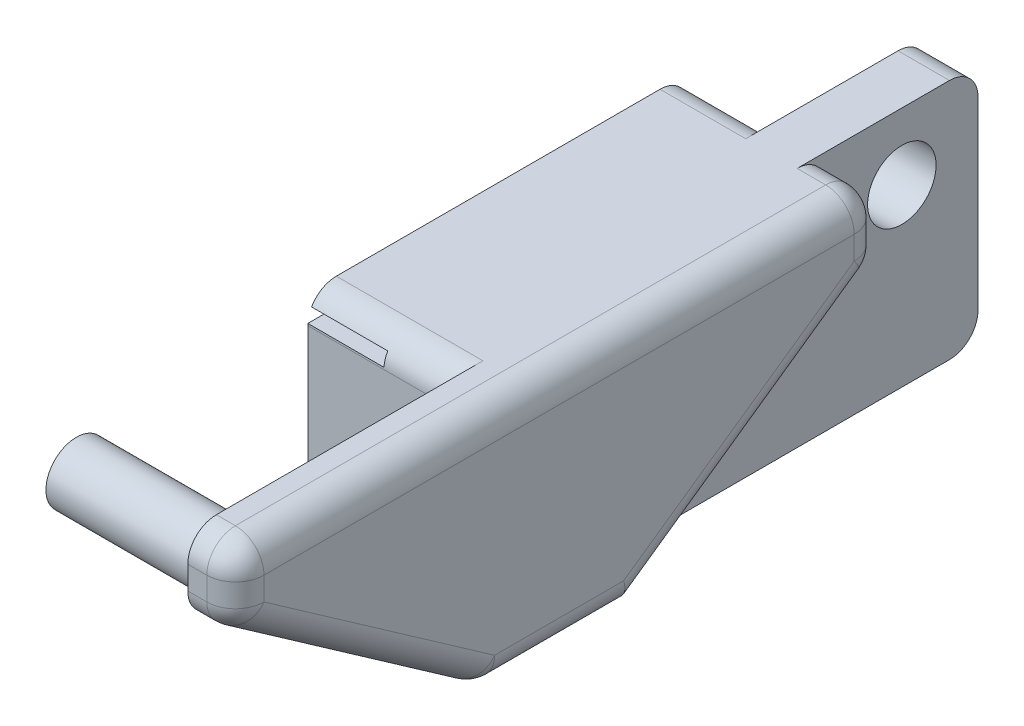
SolidWorks part; units mm, degrees
ref_plane "Front Plane" through (0, 0, 0) normal (0, 0, 1) x (1, 0, 0)
ref_plane "Top Plane" through (0, 0, 0) normal (0, 1, 0) x (1, 0, 0)
ref_plane "Right Plane" through (0, 0, 0) normal (1, 0, 0) x (0, 0, -1)
sketch "Sketch1" plane through (0, 0, 0) normal (0, 1, 0) x (1, 0, 0)
  line L0 (-28.7782, 15.5442) -> (-24.2782, 15.5442)
  line L1 (-24.2782, 15.5442) -> (-24.2782, 23.5442)
  line L2 (-24.2782, 23.5442) -> (-21.5782, 23.5442)
  line L3 (-21.5782, 23.5442) -> (-21.5782, 15.5442)
  line L4 (-21.5782, 15.5442) -> (-18.5782, 15.5442)
  line L5 (-18.5782, 15.5442) -> (-18.5782, -18.4558)
  line L6 (-18.5782, -18.4558) -> (-21.0782, -18.4558)
  line L7 (-21.0782, -18.4558) -> (-21.0782, -4.4558)
  line L10 (-21.0782, -4.4558) -> (-28.7782, -4.4558)
  line L11 (-28.7782, -4.4558) -> (-28.7782, 15.5442)
  dimension "D1" = 10.2
  dimension "D2" = 3
  dimension "D3" = 4.5
  dimension "D4" = 8
  dimension "D5" = 14
  dimension "D6" = 7.7
  dimension "D7" = 42
extrude "Boss-Extrude1" add sketch "Sketch1" along normal blind 12.7
sketch "Sketch2" plane through (-28.7782, 0, 0) normal (-1, 0, 0) x (0, 0, 1)
  line L0 (-23.5442, 12.7) -> (-23.5442, 0)
  line L1 (-23.5442, 0) -> (12.1247, 0)
  line L2 (12.1247, 0) -> (18.4558, 9.2)
  line L3 (18.4558, 9.2) -> (18.4558, 12.7)
  line L4 (18.4558, 12.7) -> (-23.5442, 12.7)
  line L5 (-23.5442, 9.2) -> (18.4558, 9.2) construction
  line L6 (-19.5442, 12.7) -> (-19.5442, 0) construction
  line L7 (-12.2942, 12.7) -> (-12.2942, 0) construction
  line L8 (15.2058, 12.7) -> (15.2058, 4.4773) construction
  line L9 (-15.5442, 5.7649) -> (-7.0404, 0)
  line L11 (4.4558, 0) -> (4.4558, 12.7)
  line L13 (-15.5442, 12.7) -> (-15.5442, 5.7649)
  line L14 (-15.5442, 12.7) -> (4.4558, 12.7)
  line L15 (12.1247, 0) -> (18.4558, 0)
  line L16 (-15.5442, 0) -> (4.4558, 0) construction
  line L17 (-15.5442, 12.7) -> (4.4558, 12.7) construction
  line L18 (-7.0404, 0) -> (4.4558, 0)
  line L19 (-15.5442, 5.7649) -> (-15.5442, 0)
  line L20 (-15.5442, 0) -> (-7.0404, 0)
  line L21 (18.4558, 0) -> (18.4558, 9.2)
  line L22 (15.2058, 10.8) -> (-23.5442, 10.8) construction
  line L23 (-23.5442, 11.3) -> (18.4558, 11.3) construction
  line L25 (18.4558, 11.95) -> (-23.5442, 11.95)
  line L26 (18.4558, 11.95) -> (18.4558, 11.3)
  line L27 (18.4558, 11.3) -> (-23.5442, 11.3)
  line L28 (-23.5442, 11.95) -> (-23.5442, 11.3)
  circle A3 centre (15.2058, 9.2) radius 1.6
  circle A4 centre (-12.2942, 9.2) radius 1.6
  circle A5 centre (-19.5442, 9.2) radius 1.8
  line M18 (-15.5442, 0) -> (4.4558, 0)
  line M21 (-15.5442, 12.7) -> (-15.5442, 0)
  dimension "D9" = 0.5
  dimension "D1" = 12.7
  dimension "D2" = 3.5
  dimension "D3" = 4
  dimension "D4" = 11.25
  dimension "D5" = 8
  dimension "D6" = 6.5
  dimension "D7" = 14
  dimension "D8" = 42
  dimension "D10" = 0.65
  dimension "D11" = 8.5038
extrude "Cut-Extrude2" cut sketch "Sketch2" along direction (1, 0, 0) on the side against the normal up to surface (4.5 mm away) contours L9 M21 M18 region at (-28.7782, 1.9216, -12.7096) up to face at (-24.2782, 6.35, -19.5442)
extrude "Cut-Extrude3" cut sketch "Sketch2<4>" against normal through all contours L15 L21 L2 region at (-28.7782, 3.0667, 16.3454)
sketch "Sketch2<4>" plane through (-28.7782, 0, 0) normal (-1, 0, 0) x (0, 0, 1) same geometry as "Sketch2"
extrude "Boss-Extrude2" add sketch "Sketch2<5>" along normal blind 9.1 from surface contours A3 region at (-28.7782, 9.2, 15.2058) starting at face at (-21.0782, 6.92, 11.5896)
sketch "Sketch2<5>" plane through (-28.7782, 0, 0) normal (-1, 0, 0) x (0, 0, 1) same geometry as "Sketch2"
extrude "Cut-Extrude4" cut sketch "Sketch2<6>" against normal through all contours A5 region at (-28.7782, 9.2, -19.5442)
sketch "Sketch2<6>" plane through (-28.7782, 0, 0) normal (-1, 0, 0) x (0, 0, 1) same geometry as "Sketch2"
extrude "Boss-Extrude3" add sketch "Sketch2<7>" along normal blind 1.4 contours A4 region at (-28.7782, 9.2, -12.2942)
sketch "Sketch2<7>" plane through (-28.7782, 0, 0) normal (-1, 0, 0) x (0, 0, 1) same geometry as "Sketch2"
extrude "Cut-Extrude5" cut sketch "Sketch2<8>" against normal blind 4 from surface contours L25 L28 L27 L26 starting at face at (-28.7782, 9.2, -13.8942)
sketch "Sketch2<8>" plane through (-28.7782, 0, 0) normal (-1, 0, 0) x (0, 0, 1) same geometry as "Sketch2"
sketch "Sketch3" plane through (-18.5782, 0, 0) normal (1, 0, 0) x (0, 0, -1)
  line L0 (15.5442, 12.7) -> (-18.4558, 12.7)
  line L3 (-18.4558, 0) -> (15.5442, 0)
  line L5 (15.5442, 12.7) -> (15.5442, 9.2)
  line L6 (15.5442, 9.2) -> (2.4052, 0)
  line L7 (2.4052, 0) -> (-1.4558, 0)
  line L8 (15.5442, 9.2) -> (15.5442, 0)
  line L9 (15.5442, 0) -> (2.4052, 0)
  line L10 (-1.4558, 12.7) -> (-1.4558, 0)
  line L11 (-18.4558, 0) -> (-5.3168, 0)
  line L12 (-18.4558, 9.2) -> (-18.4558, 0)
  line L13 (-18.4558, 9.2) -> (-5.3168, 0)
  line L14 (-18.4558, 12.7) -> (-18.4558, 9.2)
  line M7 (-18.4558, 9.2) -> (-12.1247, 0)
  line M8 (-12.1247, 0) -> (15.5442, 0)
  line M9 (15.5442, 0) -> (15.5442, 12.7)
  dimension "D1" = 13.139
  dimension "D3" = 9.2
  dimension "D4" = 12.7
extrude "Cut-Extrude6" cut sketch "Sketch3" against normal up to surface (3 mm away) contours L6 L3 M9 | L12 L3 M7 | L13 M7 M8 region at (-18.5782, 3.0667, -11.1645) region at (-18.5782, 3.0667, 16.3454) region at (-18.5782, 3.0667, 11.9658) up to face at (-21.5782, 9.2, -17.7442)
sketch "Sketch4" plane through (0, 0, 0) normal (0, -1, 0) x (1, 0, 0)
  line L0 (-22.9282, -23.5442) -> (-22.9282, 4.4558) construction
  line L1 (-21.5782, -23.5442) -> (-24.2782, -23.5442) construction
  line L2 (-28.7782, 4.4558) -> (-21.0782, 4.4558) construction
  line L4 (-22.1782, -23.5442) -> (-23.6782, -23.5442)
  line L5 (-22.1782, -23.5442) -> (-22.1782, 4.4558)
  line L6 (-22.1782, 4.4558) -> (-23.6782, 4.4558)
  line L7 (-23.6782, -23.5442) -> (-23.6782, 4.4558)
  dimension "D1" = 0.75
  dimension "D2" = 0.75
extrude "Cut-Extrude7" cut sketch "Sketch4" against normal blind 3
sketch "Sketch6" plane through (0, 0, 0) normal (0, -1, 0) x (-1, 0, 0)
  line L1 (23.6782, -4.4558) -> (21.5782, -4.4558)
  line L2 (23.6782, -4.4558) -> (23.6782, 2.4052)
  line L3 (23.6782, 2.4052) -> (21.5782, 2.4052)
  line L4 (21.5782, -4.4558) -> (21.5782, 2.4052)
extrude "Boss-Extrude4" add sketch "Sketch6" against normal blind 1
sketch "Sketch8" plane through (-28.7782, 0, 0) normal (-1, 0, 0) x (0, 0, 1)
  line L0 (1.4558, 12.7) -> (-15.5442, 12.7)
  line L1 (-15.5442, 0) -> (1.4558, 0)
  line L7 (1.4558, 12.7) -> (1.4558, 0)
  line L8 (-15.5442, 0) -> (-2.4052, 0)
  line L9 (-15.5442, 9.2) -> (-15.5442, 0)
  line L10 (-15.5442, 9.2) -> (-2.4052, 0)
  line L11 (-15.5442, 12.7) -> (-15.5442, 9.2)
  line M7 (-15.5442, 5.7649) -> (-7.0404, 0)
  line M9 (-7.0404, 0) -> (4.4558, 0)
  line M19 (-15.5442, 11.3) -> (-15.5442, 5.7649)
  dimension "D1" = 13.139
  dimension "D2" = 12.7
  dimension "D3" = 9.2
  dimension "D4" = 17
extrude "Cut-Extrude8" cut sketch "Sketch8" against normal up to surface (4.5 mm away) contours L9 L1 M7 | L10 M19 M7 M9 region at (-28.7782, 3.8479, -10.1104) region at (-28.7782, 1.9216, -12.7096) up to face at (-24.2782, 9.2, -21.3442)
fillet "Fillet1" radius 1.5 19 edges at (-24.9282, 0, 4.4558) (-24.9282, 12.7, 4.4558) (-21.8782, 0, -23.5442) (-23.9782, 0, -23.5442) (-22.9282, 12.7, -23.5442) (-18.5782, 10.95, 18.4558) (-19.8282, 9.2, 18.4558) (-19.8282, 12.7, 18.4558) (-19.8282, 0, 5.3168) (-18.5782, 4.6, 11.8863) (-18.5782, 0, 1.4558) (-18.5782, 4.6, -8.9747) (-20.0782, 9.2, -15.5442) (-18.5782, 10.95, -15.5442) (-26.5282, 12.7, -15.5442) (-20.0782, 12.7, -15.5442) (-18.5782, 12.7, 1.4558) (-26.5282, 0, -2.4052) (-26.5282, 9.2, -15.5442)
fillet "Fillet2" radius 0.25 14 edges at (-23.6782, 0, -12.2247) (-22.1782, 0, -12.2247) (-23.6782, 0.4393, -23.1049) (-22.1782, 0.4393, -23.1049) (-23.6782, 1.2463, 4.4342) (-22.1782, 1.2463, 4.4342) (-23.6782, 2.25, -23.5442) (-22.1782, 2.25, -23.5442) (-23.6782, 2.25, 4.4558) (-22.1782, 2.25, 4.4558) (-22.9282, 3, -23.5442) (-23.6782, 3, -9.5442) (-22.9282, 3, 4.4558) (-22.1782, 3, -9.5442)
